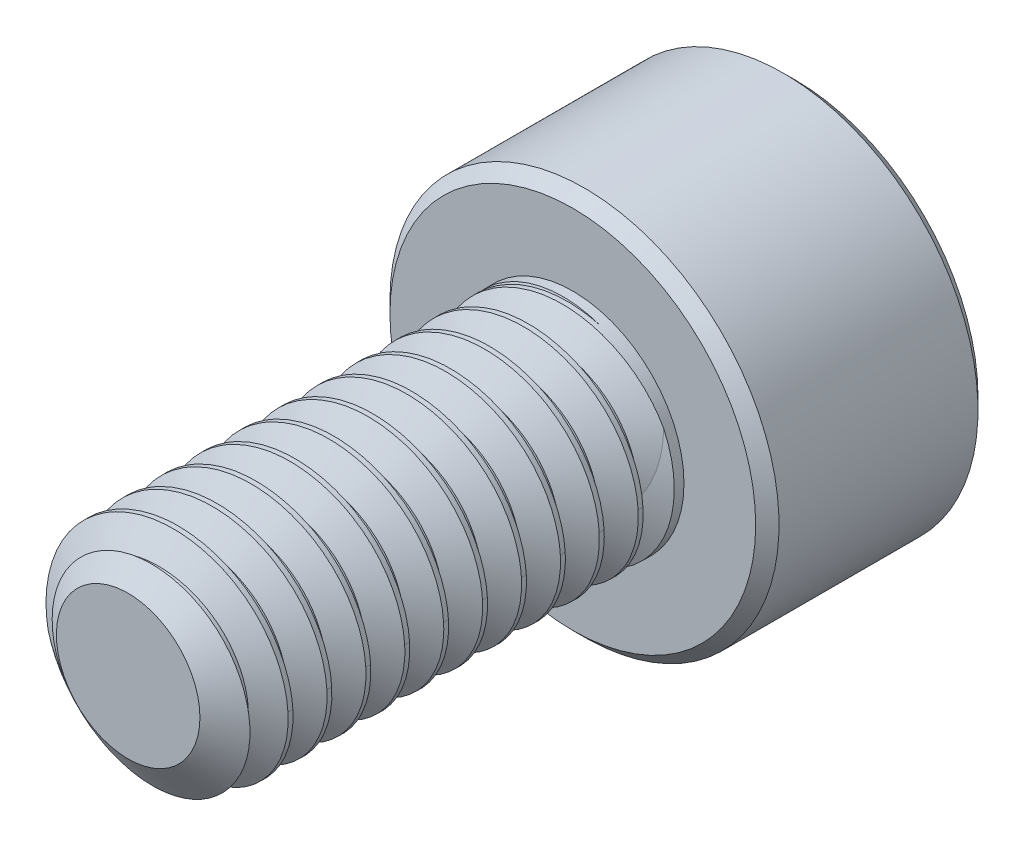
SolidWorks part; units mm, degrees
ref_plane "Front Plane" through (0, 0, 0) normal (0, 0, 1) x (1, 0, 0)
ref_plane "Top Plane" through (0, 0, 0) normal (0, 1, 0) x (1, 0, 0)
ref_plane "Right Plane" through (0, 0, 0) normal (1, 0, 0) x (0, 0, -1)
sketch "Sketch1" plane through (0, 0, 0) normal (0, 0, 1) x (1, 0, 0)
  circle A0 centre (0, 0) radius 2
  dimension "OD" = 4
extrude "Extrude1" add sketch "Sketch1" against normal blind 8
sketch "Sketch2" plane through (0, 0, 0) normal (0, 0, 1) x (1, 0, 0)
  circle A0 centre (0, 0) radius 2 construction
  circle A1 centre (0, 0) radius 2
curve "Helix/Spiral1" pitch 0.7 height 8.7 radius 2 centre (0, 0, 0) axis (0, 0, -1) start towards (0, 1, 0) parameters "pitch"=0.7
sketch "Sketch3" plane through (0, 0, 0) normal (1, 0, 0) x (0, 0, -1)
  line L0 (-0.6125, 2) -> (-0.35, 1.5453)
  line L1 (-0.35, 1.5453) -> (-0.2625, 1.5453)
  line L2 (-0.2625, 1.5453) -> (0, 2)
  line L3 (-0.6125, 2) -> (0, 2)
  line L4 (-0.3063, 2) -> (-0.3063, 1.5453) construction
  line L5 (-0.4813, 1.7727) -> (-0.1313, 1.7727) construction
  line L6 (0, 2) -> (0, -2) construction
  line L7 (0, -2) -> (8, -2) construction
  point P11 (3.15, -2)
  dimension "D1" = 0.0875
  dimension "D2" = 0.35
  dimension "D3" = 60
  dimension "D4" = 3.15
sweep "Cut-Sweep1" cut profiles "Sketch3" path "Helix/Spiral1" align with end faces yes
sketch "Sketch4" plane through (0, 0, 0) normal (1, 0, 0) x (0, 0, -1)
  line L0 (0.4962, 2) -> (0, 1.2913)
  line L1 (0, 1.2913) -> (0, 2)
  line L2 (0.4962, 2) -> (0, 2)
  line L3 (-0.6125, 2) -> (0, 2) construction
  line L4 (0, 0) -> (7.0209, 0) construction
  dimension "D1" = 55
  dimension "D2" = 0.254
revolve "Cut-Revolve1" cut sketch "Sketch4" angle 360 about L4
sketch "Sketch5" plane through (0, 0, 0) normal (1, 0, 0) x (0, 0, -1)
  line L0 (8, -0.6429) -> (8, 1.6418) construction
  line L1 (8, 2) -> (0.1203, 2)
  line L2 (8, 2) -> (8, 0)
  line L3 (8, 0) -> (0.0001, 0)
  line L4 (0.0001, 1.6698) -> (0.0001, 0)
  line L5 (0.1203, 2) -> (0.0001, 1.6698)
  line L6 (0, 0) -> (9.9695, 0) construction
  point P3 (0.0001, 2)
  point P10 (0.0001, 2)
  dimension "D1" = 0.3302
  dimension "Thread min" = 0.0001
  dimension "D3" = 20
revolve "partially thread" [suppressed] add sketch "Sketch5" angle 360 about L6
sketch "Sketch6" plane through (0, 0, -8) normal (0, 0, -1) x (-1, 0, 0)
  circle A0 centre (0, 0) radius 3.5
  dimension "head dia" = 7
extrude "Extrude2" add sketch "Sketch6" along normal blind 4
sketch "Sketch7" plane through (0, 0, -12) normal (0, 0, -1) x (-1, 0, 0)
  line L1 (0, 1.7321) -> (-1.5, 0.866)
  line L2 (-1.5, 0.866) -> (-1.5, -0.866)
  line L3 (-1.5, -0.866) -> (0, -1.7321)
  line L4 (0, -1.7321) -> (1.5, -0.866)
  line L5 (1.5, -0.866) -> (1.5, 0.866)
  line L6 (1.5, 0.866) -> (0, 1.7321)
  circle A0 centre (0, 0) radius 1.5 construction
  dimension "hex dia" = 3
extrude "Cut-Extrude1" cut sketch "Sketch7" against normal blind 2.25
sketch "Sketch8" plane through (0, 0, -12) normal (0, 0, -1) x (-1, 0, 0)
  circle A0 centre (0, 0) radius 1.7321
extrude "Cut-Extrude2" cut sketch "Sketch8" against normal through all draft 45
chamfer "Chamfer1" distance 0.21 angle 45 2 edges at (-3.5, 0, -12) (-3.5, 0, -8)
sketch "Sketch9" plane through (0, 0, 0) normal (1, 0, 0) x (0, 0, -1)
  line L0 (0, 2) -> (0, -2) construction
  line L1 (3.85, 2) -> (3.85, -2) construction
  dimension "D1" = 3.85
sketch "Sketch10" plane through (0, 0, 0) normal (1, 0, 0) x (0, 0, -1)
  line L0 (8, 2) -> (8, 0)
  line L1 (8, 2) -> (7.825, 2)
  line L2 (7.825, 2) -> (6.9966, 0)
  line L3 (8, 0) -> (6.9966, 0)
  line L4 (8, 3.29) -> (8, -3.29) construction
  dimension "D1" = 22.5
  dimension "D2" = 0.175
revolve "Revolve1" add sketch "Sketch10" angle 360 about L3
equation "\"D3@Helix/Spiral1\" = \"screw length@Extrude1\"+\"pitch@Helix/Spiral1\""
equation "\"D1@Sketch3\" = \"pitch@Helix/Spiral1\"*.125"
equation "\"D2@Sketch3\" = \"pitch@Helix/Spiral1\"*.5"
equation "\"D1@Cut-Extrude1\" = \"hex dia@Sketch7\"*.75"
equation "\"D1@Chamfer1\" = \"head dia@Sketch6\"*.03"
equation "\"D1@Sketch9\" = \"pitch@Helix/Spiral1\"*5.5"
equation "\"D2@Sketch10\" = \"pitch@Helix/Spiral1\"*.25"
equation "\"D4@Sketch3\" = \"pitch@Helix/Spiral1\"*4.50"
